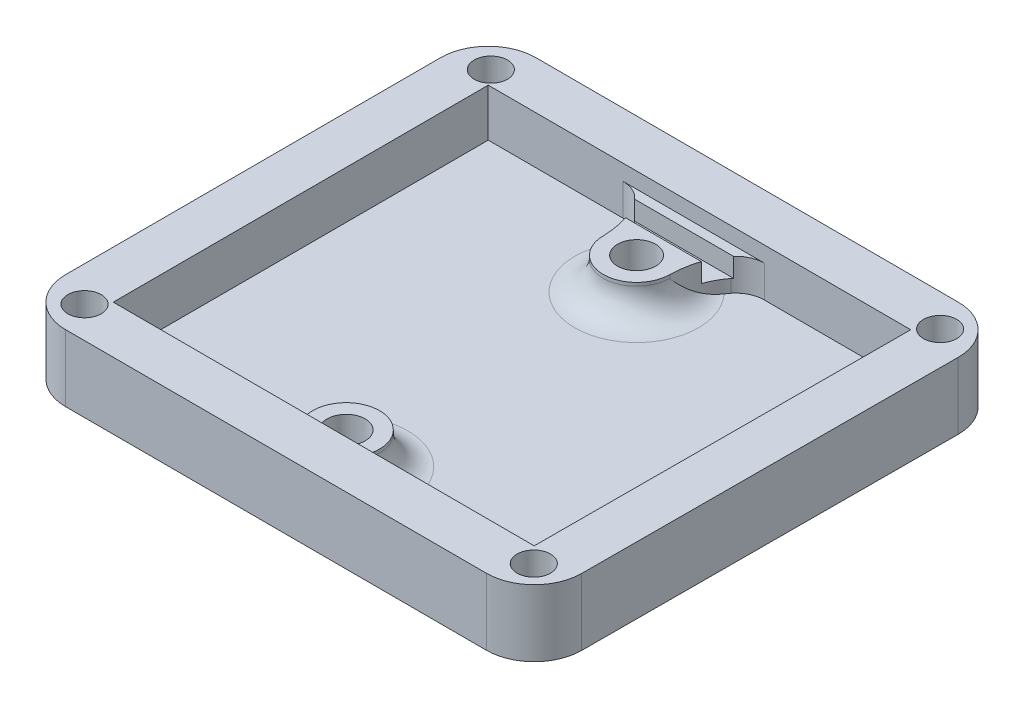
SolidWorks part; units mm, degrees
ref_plane "Alzado" through (0, 0, 0) normal (0, 0, 1) x (1, 0, 0)
ref_plane "Planta" through (0, 0, 0) normal (0, 1, 0) x (1, 0, 0)
ref_plane "Vista lateral" through (0, 0, 0) normal (1, 0, 0) x (0, 0, -1)
sketch "Croquis1" plane through (0, 0, 0) normal (0, 1, 0) x (1, 0, 0)
  line L0 (0.2076, -18.5094) -> (22.3262, -18.7144)
  line L1 (22.3262, -18.7144) -> (22.443, 20.6853)
  line L2 (22.443, 20.6853) -> (-21.957, 20.7442)
  line L3 (-21.957, 20.7442) -> (-21.9107, -18.6558)
  line L4 (-21.9107, -18.6558) -> (22.3262, -18.7144)
  circle A0 centre (-0.367, 14.7242) radius 1.3
  circle A1 centre (0.268, -16.3908) radius 1.3
  dimension "D1" = 44.4
  dimension "D2" = 39.4
  dimension "D3" = 21.5829
  dimension "D4" = 22.1813
  dimension "D5" = 2.1195
  dimension "D6" = 5.9913
extrude "Saliente-Extruir1" add sketch "Croquis1" along normal blind 5 contours L3 L4 L0 L1 L2 A1 A0 region at (0.2271, 0, -1.0383)
shell "Vaciado1" thickness 5 removed face at (0.2254, 5, -1.0149) outward yes
sketch "Croquis2" plane through (0, 5, 0) normal (0, 1, 0) x (1, 0, 0)
  line L0 (-0.367, 14.7242) -> (-0.367, 13.4242) construction
  line L2 (-6.6406, 20.7239) -> (5.9066, 20.7239)
  circle A0 centre (-0.367, 14.7242) radius 2
  circle A1 centre (0.268, -16.3908) radius 2
  arc A2 (-3.867, 14.7242) -> (3.133, 14.7242) centre (-0.367, 14.7242) ccw
  circle A3 centre (0.268, -16.3908) radius 3.5
  circle A4 centre (-0.367, 14.7242) radius 1.3 construction
  spline S0 degree 2 poles (-3.867, 14.7242) (-4.0058, 18.79) (-6.6406, 20.7239) knots 0 0 0 0.918206 0.918206 0.918206
  spline S1 degree 2 poles (3.133, 14.7242) (3.2719, 18.79) (5.9066, 20.7239) knots 0 0 0 0.918206 0.918206 0.918206
  dimension "D1" = 4
  dimension "D2" = 4
  dimension "D3" = 7
  dimension "D4" = 7
extrude "Saliente-Extruir2" add sketch "Croquis2" against normal up to surface (5 mm away) from offset 1.65 up to face at (0.2254, 0, -1.0149) offset against normal yes
sketch "Croquis3" plane through (0, 5, 0) normal (0, 1, 0) x (1, 0, 0)
  circle A0 centre (-0.367, 14.7242) radius 2
  circle A1 centre (0.268, -16.3908) radius 2
extrude "Cortar-Extruir1" cut sketch "Croquis3" against normal up to surface (5 mm away) up to face at (-0.004, 0, -3.3872)
fillet "Redondeo1" radius 5 2 edges at (27.4579, 0, -25.6787) (-26.9628, 0, -25.7509)
sketch "Croquis4" plane through (0, 5, 0) normal (0, 1, 0) x (1, 0, 0)
  line L0 (0, 0) -> (0, -4.5498) construction
  line L1 (0, 0) -> (-3.9144, 0) construction
  circle A1 centre (-23.233, -20.3506) radius 1.75
  circle A2 centre (23.9188, -20.3506) radius 1.75
  circle A3 centre (23.9188, 22.2917) radius 1.75
  circle A6 centre (-23.233, 22.2917) radius 1.75
  point P7 (23.9188, 22.2917)
  point P11 (-23.233, -20.3506)
  point P13 (0, 0)
  point P15 (-23.233, 22.2917)
  dimension "D1" = 3.5
extrude "Cortar-Extruir2" cut sketch "Croquis4" against normal blind 4
fillet "Redondeo2" radius 3 4 edges at (0.2727, 0, 12.8908) (-0.367, 0, -11.2242) (5.8841, 1.675, -20.7073) (-6.6406, 1.675, -20.7239)
sketch "Croquis5" plane through (0, 3.35, 0) normal (0, 1, 0) x (1, 0, 0)
  line L1 (-5.6511, 19.7093) -> (5.0591, 19.7093)
  line L2 (-5.6511, 19.7093) -> (-5.6511, 17.5482)
  line L3 (-5.6511, 17.5482) -> (5.0591, 17.5482)
  line L4 (5.0591, 19.7093) -> (5.0591, 17.5482)
  line L5 (-5.6511, 19.7093) -> (5.0591, 17.5482) construction
  line L6 (-5.6511, 17.5482) -> (5.0591, 19.7093) construction
  point P0 (-0.296, 18.6287)
  point P5 (-0.296, 18.2093)
  point P6 (0, 0)
extrude "Cortar-Extruir3" cut sketch "Croquis5" against normal blind 2
fillet "Redondeo3" radius 5 2 edges at (-26.9048, 0, 23.6492) (27.3114, 0, 23.721)
sketch "Croquis6" plane through (0, -5, 0) normal (0, -1, 0) x (1, 0, 0)
  line L1 (-67.6171, 58.5505) -> (66.7762, 58.5505)
  line L2 (-67.6171, 58.5505) -> (-67.6171, -58.5505)
  line L3 (-67.6171, -58.5505) -> (66.7762, -58.5505)
  line L4 (66.7762, 58.5505) -> (66.7762, -58.5505)
  line L5 (-67.6171, 58.5505) -> (66.7762, -58.5505) construction
  line L6 (-67.6171, -58.5505) -> (66.7762, 58.5505) construction
  point P0 (-0.4204, 0)
extrude "Cortar-Extruir4" cut sketch "Croquis6" against normal blind 3
